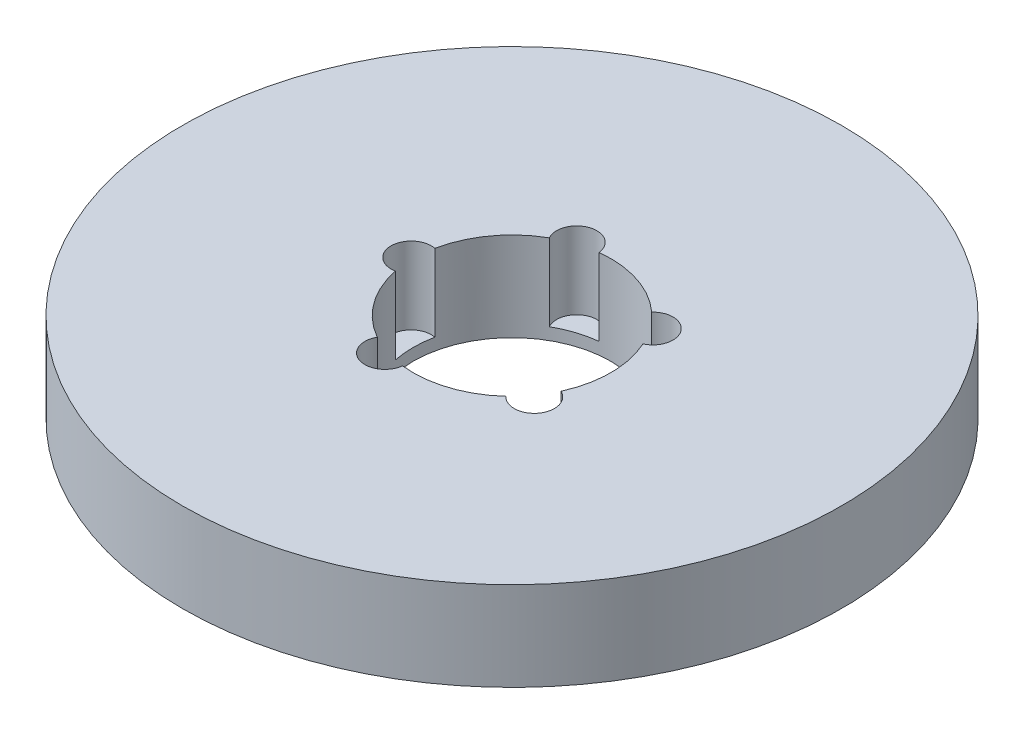
SolidWorks part; units mm, degrees
ref_plane "Front Plane" through (0, 0, 0) normal (0, 0, 1) x (1, 0, 0)
ref_plane "Top Plane" through (0, 0, 0) normal (0, 1, 0) x (1, 0, 0)
ref_plane "Right Plane" through (0, 0, 0) normal (1, 0, 0) x (0, 0, -1)
sketch "Sketch1" plane through (0, 0, 0) normal (0, 1, 0) x (1, 0, 0)
  circle A0 centre (0, 0) radius 100
  dimension "FLANGE_OD" = 200
extrude "Boss-Extrude1" add sketch "Sketch1" along normal blind 27
sketch "Sketch2" plane through (0, 0, 0) normal (0, 1, 0) x (1, 0, 0)
  circle A0 centre (0, 0) radius 30
  dimension "BORE_D" = 60
extrude "Cut-Extrude1" cut sketch "Sketch2" along normal through all
sketch "Sketch3" plane through (0, 27, 0) normal (0, 1, 0) x (1, 0, 0)
  circle A0 centre (0, 0) radius 30.5913 construction
  circle A1 centre (-30.5913, 0) radius 6.1038
  dimension "BOLT_D" = 12.2076
  dimension "BOLT_PCD" = 61.1825
extrude "Cut-Extrude2" cut sketch "Sketch3" against normal blind 23.3552
pattern_circular "CirPattern1" count 5 over 360 about axis through (0, 0, 0) along (0, 1, 0) of "Cut-Extrude2"
